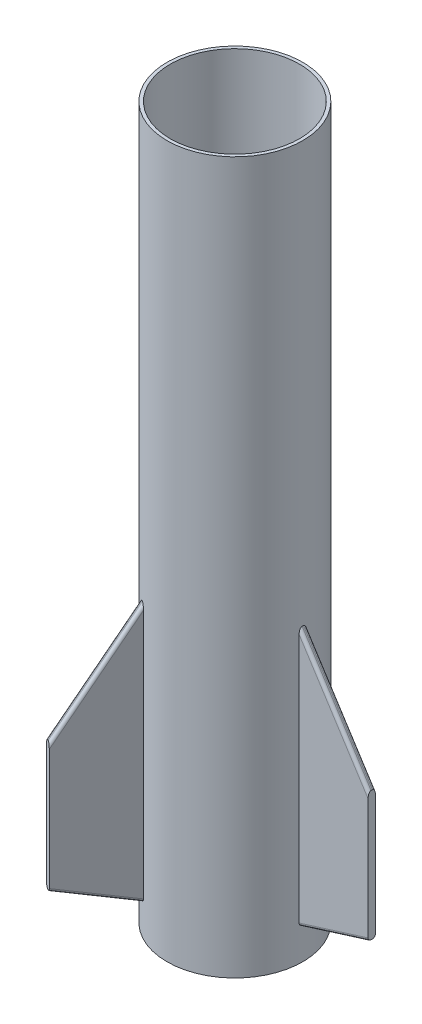
SolidWorks part; units mm, degrees
ref_plane "Front Plane" through (0, 0, 0) normal (0, 0, 1) x (1, 0, 0)
ref_plane "Top Plane" through (0, 0, 0) normal (0, 1, 0) x (1, 0, 0)
ref_plane "Right Plane" through (0, 0, 0) normal (1, 0, 0) x (0, 0, -1)
sketch "Sketch3" plane through (0, 0, 0) normal (0, 1, 0) x (1, 0, 0)
  circle A0 centre (0, 0) radius 40.005
  circle A1 centre (0, 0) radius 38.1
  dimension "D1" = 80.01
  dimension "D2" = 76.2
extrude "Boss-Extrude1" add sketch "Sketch3" along normal blind 419.1
sketch "Sketch4" plane through (0, 0, 0) normal (0, 0, 1) x (1, 0, 0)
  line L0 (40.005, 19.05) -> (40.005, 171.45)
  line L1 (40.005, 0) -> (40.005, 419.1) construction
  line L2 (40.005, 171.45) -> (80.645, 107.95)
  line L3 (80.645, 107.95) -> (80.645, 31.75)
  line L4 (80.645, 31.75) -> (40.005, 19.05)
  dimension "D1" = 76.2
  dimension "D2" = 152.4
  dimension "D3" = 40.64
  dimension "D4" = 12.7
  dimension "D5" = 19.05
extrude "Boss-Extrude2" add sketch "Sketch4" along normal blind 2.159 and the other way blind 2.159 separate body
fillet "Fillet1" radius 1.778 4 edges at (60.325, 25.4, 2.159) (60.325, 25.4, -2.159) (60.325, 139.7, 2.159) (60.325, 139.7, -2.159)
sketch "Sketch5" plane through (0, 0, 0) normal (0, 0, 1) x (1, 0, 0)
  line L0 (0, 0) -> (0, 465.0168) construction
pattern_circular "CirPattern1" count 3 over 360 about axis through (0, 0, 0) along (0, 1, 0) reverse direction yes of bodies 102
